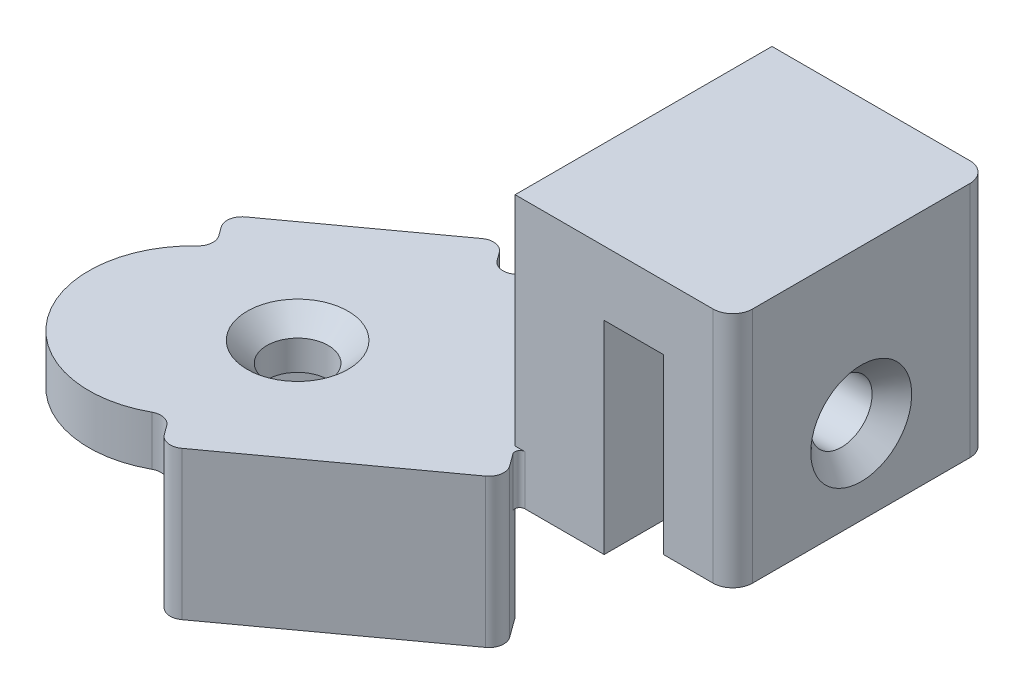
SolidWorks part; units mm, degrees
material "PA 类型 6"
ref_plane "前视基准面" through (0, 0, 0) normal (0, 0, 1) x (1, 0, 0)
ref_plane "上视基准面" through (0, 0, 0) normal (0, 1, 0) x (1, 0, 0)
ref_plane "右视基准面" through (0, 0, 0) normal (1, 0, 0) x (0, 0, -1)
sketch "草图1" plane through (0, 0, 0) normal (0, 1, 0) x (1, 0, 0)
  line L0 (0, 0) -> (0, 12.2017) construction
  line L1 (0, 0) -> (15.21, 0) construction
  line L2 (0, 0) -> (11.3188, 8.2236) construction
  line L3 (10.1244, 13.8452) -> (-6.1542, 2.018)
  line L4 (10.1244, 0.8664) -> (0.0175, -6.4766)
  line L5 (0.0175, -6.4766) -> (-6.1542, 2.018) construction
  line L6 (10.1244, 13.8452) -> (10.1244, 0.8664)
  circle A0 centre (0, 0) radius 1.55
  arc A1 (-6.1542, 2.018) -> (0.0175, -6.4766) centre (-3.0684, -2.2293) ccw
  dimension "D1" = 3.1
  dimension "D2" = 36
  dimension "D3" = 10.5
  dimension "D4" = 10.1244
extrude "基座" add sketch "草图1" along normal blind 2.5
sketch "草图2" plane through (0, 0, 0) normal (0, 1, 0) x (1, 0, 0)
  line L0 (0.0175, -6.4766) -> (1.1931, -8.0947)
  line L1 (1.1931, -8.0947) -> (11.3, -0.7516)
  line L2 (11.3, -0.7516) -> (10.1244, 0.8664)
  line L3 (0.0175, -6.4766) -> (10.1244, 0.8664) construction
  line L4 (10.1244, 0.8664) -> (0.0175, -6.4766)
  line L5 (0, 0) -> (19.4408, 0) construction
  line L6 (0, 0) -> (14.65, 10.6439) construction
  line L7 (10.1244, 13.8452) -> (-6.1542, 2.018) construction
  line L8 (10.1244, 13.8452) -> (-6.1542, 2.018) construction
  line L10 (-7.3298, 3.6361) -> (0.8095, 9.5496)
  line L11 (-6.1542, 2.018) -> (-7.3298, 3.6361)
  line L12 (1.9851, 7.9316) -> (-6.1542, 2.018)
  line L13 (0.8095, 9.5496) -> (1.9851, 7.9316)
  point P20 (1.9851, 7.9316)
  dimension "D1" = 2
extrude "机臂限位" add sketch "草图2" against normal blind 7.5 from surface starting at face at (2.4662, 2.5, -1.7918)
sketch "草图3" plane through (0, 0, 0) normal (0, 1, 0) x (1, 0, 0)
  line L0 (10.1244, 13.8452) -> (14.6244, 13.8452)
  line L1 (14.6244, 13.8452) -> (14.6244, 0.8664)
  line L2 (14.6244, 0.8664) -> (10.1244, 0.8664)
  line L3 (10.1244, 0.8664) -> (10.1244, 13.8452)
  dimension "D1" = 4.5
extrude "限位-1" add sketch "草图3" along normal blind 13.5
sketch "草图4" plane through (0, 0, 0) normal (0, 0, 1) x (1, 0, 0)
  line L0 (14.6244, 13.5) -> (21.1244, 13.5)
  line L1 (21.1244, 13.5) -> (21.1244, 1.5)
  line L2 (21.1244, 1.5) -> (17.6244, 1.5)
  line L3 (17.6244, 1.5) -> (17.6244, 10.25)
  line L4 (17.6244, 10.25) -> (14.6244, 10.25)
  line L5 (14.6244, 13.5) -> (14.6244, 0) construction
  line L6 (14.6244, 10.25) -> (14.6244, 13.5)
  dimension "D1" = 3.25
  dimension "D2" = 3
  dimension "D3" = 8.75
  dimension "D4" = 3.5
extrude "限位-2" add sketch "草图4" against normal up to surface (13.8452 mm away) from surface up to face at (11.9244, 5.9, -13.8452) starting at face at (11.9244, 5.9, -0.8664)
sketch "草图5" plane through (21.1244, 0, 0) normal (1, 0, 0) x (0, 0, -1)
  line L2 (7.3558, 5.75) -> (7.3558, 13.5) construction
  line L3 (13.8452, 13.5) -> (0.8664, 13.5) construction
  line L5 (8.9579, 2.975) -> (10.5601, 5.75)
  line L6 (10.5601, 5.75) -> (8.9579, 8.525)
  line L7 (8.9579, 8.525) -> (5.7537, 8.525)
  line L8 (5.7537, 8.525) -> (4.1515, 5.75)
  line L9 (4.1515, 5.75) -> (5.7537, 2.975)
  line L10 (5.7537, 2.975) -> (8.9579, 2.975)
  circle A0 centre (7.3558, 5.75) radius 1.55
  circle A1 centre (7.3558, 5.75) radius 2.775 construction
  dimension "D1" = 3.1
  dimension "D2" = 5.55
  dimension "D3" = 7.75
extrude "螺丝位" cut sketch "草图5" against normal through all contours A0 region at (21.1244, 5.75, -7.3558)
extrude "螺母位" cut sketch "草图5<3>" along normal blind 2 from surface starting at face at (10.1244, 5.75, -8.9058)
sketch "草图5<3>" plane through (21.1244, 0, 0) normal (1, 0, 0) x (0, 0, -1) same geometry as "草图5"
chamfer "倒角1" distance 1 angle 45 2 edges at (21.1244, 7.3, -7.3558) (0, 2.5, 1.55)
fillet "圆角5" radius 0.75 7 edges at (1.1931, -1.25, 8.0947) (-7.3298, -1.25, -3.6361) (0.0175, 1.25, 6.4766) (-6.1542, 1.25, -2.018) (11.3, -1.25, 0.7516) (1.9851, 1.25, -7.9316) (0.8095, -1.25, -9.5496)
fillet "圆角6" radius 0.25 1 edges at (10.1244, 1.25, -0.8664)
fillet "圆角8" radius 1 2 edges at (21.1244, 7.5, -0.8664) (21.1244, 7.5, -13.8452)
